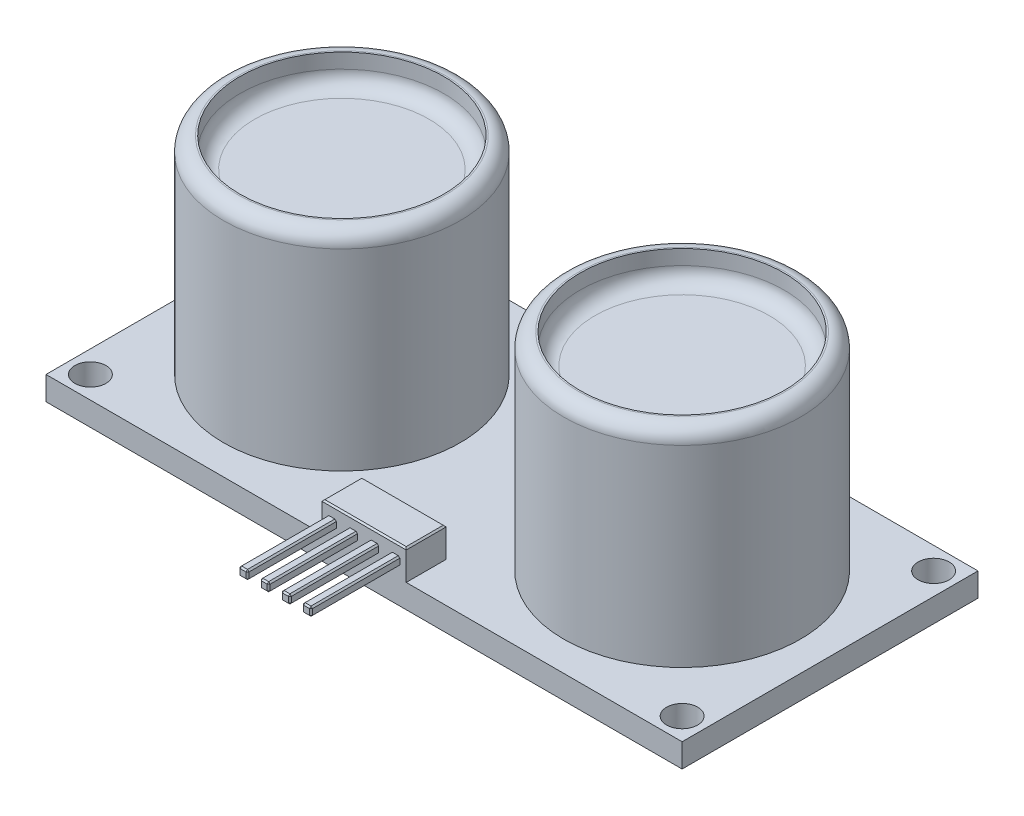
SolidWorks part; units mm, degrees
ref_plane "Front Plane" through (0, 0, 0) normal (0, 0, 1) x (1, 0, 0)
ref_plane "Top Plane" through (0, 0, 0) normal (0, 1, 0) x (1, 0, 0)
ref_plane "Right Plane" through (0, 0, 0) normal (1, 0, 0) x (0, 0, -1)
sketch "Sketch1" plane through (0, 0, 0) normal (0, 1, 0) x (1, 0, 0)
  line L0 (21.5, 20) -> (21.5, 0) construction
  line L1 (0, 0) -> (43, 0)
  line L2 (0, 0) -> (0, 20)
  line L3 (0, 20) -> (43, 20)
  line L4 (43, 0) -> (43, 20)
  dimension "D1" = 20
  dimension "D2" = 43
extrude "Boss-Extrude1" add sketch "Sketch1" along normal blind 1.6
sketch "Sketch2" plane through (0, 1.6, 0) normal (0, 1, 0) x (1, 0, 0)
  line L0 (0, 10) -> (43, 10) construction
  line L1 (0, 20) -> (0, 0) construction
  line L2 (43, 0) -> (43, 20) construction
  circle A0 centre (10, 10) radius 8
  dimension "D1" = 16
  dimension "D2" = 10
extrude "Boss-Extrude2" add sketch "Sketch2" along normal blind 14
sketch "Sketch3" plane through (0, 15.6, 0) normal (0, 1, 0) x (1, 0, 0)
  circle A0 centre (10, 10) radius 6.894
extrude "Cut-Extrude1" cut sketch "Sketch3" against normal blind 2
fillet "Fillet1" radius 1 1 edges at (10, 15.6, -2)
fillet "Fillet2" radius 1 1 edges at (10, 13.6, -3.106)
ref_axis "Axis1" through (21.5, 0, -20) along (0, 0, 1)
ref_plane "Plane1" through (21.5, 0, 0) normal (1, 0, 0) x (0, 0, -1)
mirror "Mirror1" about plane through (21.5, 0, 0) normal (1, 0, 0) of "Fillet2", "Fillet1", "Cut-Extrude1", "Boss-Extrude2"
sketch "Sketch4" plane through (0, 1.6, 0) normal (0, 1, 0) x (1, 0, 0)
  line L0 (21.5, 0) -> (18.65, 0)
  line L1 (0, 0) -> (43, 0) construction
  line L2 (21.5, 0) -> (24.35, 0)
  line L3 (18.65, 0) -> (18.65, 2.7)
  line L4 (18.65, 2.7) -> (24.35, 2.7)
  line L5 (24.35, 2.7) -> (24.35, 0)
  dimension "D1" = 2.85
  dimension "D2" = 2.85
  dimension "D3" = 2.7
extrude "Boss-Extrude3" add sketch "Sketch4" along normal blind 2
sketch "Sketch5" plane through (0, 0, 0) normal (0, 0, 1) x (1, 0, 0)
  line L0 (18.65, 2.6) -> (24.35, 2.6) construction
  line L1 (18.65, 3.6) -> (18.65, 1.6) construction
  line L2 (24.35, 3.6) -> (24.35, 1.6) construction
  line L3 (20.4525, 2.3) -> (21.0525, 2.9) construction
  line L4 (19.0225, 2.3) -> (19.6225, 2.3)
  line L5 (19.0225, 2.3) -> (19.0225, 2.9)
  line L6 (19.0225, 2.9) -> (19.6225, 2.9)
  line L7 (19.6225, 2.3) -> (19.6225, 2.9)
  line L8 (19.0225, 2.3) -> (19.6225, 2.9) construction
  line L9 (19.0225, 2.9) -> (19.6225, 2.3) construction
  line L10 (20.4525, 2.9) -> (21.0525, 2.3) construction
  line L11 (20.4525, 2.3) -> (20.4525, 2.9)
  line L12 (20.4525, 2.3) -> (21.0525, 2.3)
  line L13 (21.0525, 2.3) -> (21.0525, 2.9)
  line L14 (20.4525, 2.9) -> (21.0525, 2.9)
  line L15 (21.8825, 2.3) -> (22.4825, 2.9) construction
  line L16 (21.8825, 2.9) -> (22.4825, 2.3) construction
  line L17 (21.8825, 2.3) -> (21.8825, 2.9)
  line L18 (21.8825, 2.3) -> (22.4825, 2.3)
  line L19 (22.4825, 2.3) -> (22.4825, 2.9)
  line L20 (21.8825, 2.9) -> (22.4825, 2.9)
  line L21 (23.3125, 2.3) -> (23.9125, 2.9) construction
  line L22 (23.3125, 2.9) -> (23.9125, 2.3) construction
  line L23 (23.3125, 2.3) -> (23.3125, 2.9)
  line L24 (23.3125, 2.3) -> (23.9125, 2.3)
  line L25 (23.9125, 2.3) -> (23.9125, 2.9)
  line L26 (23.3125, 2.9) -> (23.9125, 2.9)
  point P6 (19.3225, 2.6)
  point P12 (20.7525, 2.6)
  point P17 (22.1825, 2.6)
  point P22 (23.6125, 2.6)
  dimension "D1" = 0.6
  dimension "D2" = 4
extrude "Boss-Extrude4" add sketch "Sketch5" along normal blind 6
chamfer "Chamfer1" distance 0.1 angle 45 32 edges at (23.9125, 2.6, 6) (23.9125, 2.3, 3) (23.6125, 2.3, 6) (23.3125, 2.3, 3) (23.3125, 2.6, 6) (23.9125, 2.9, 3) (23.6125, 2.9, 6) (23.3125, 2.9, 3) (22.4825, 2.6, 6) (22.4825, 2.3, 3) (22.1825, 2.3, 6) (21.8825, 2.3, 3) (21.8825, 2.6, 6) (21.8825, 2.9, 3) (22.1825, 2.9, 6) (22.4825, 2.9, 3) (21.0525, 2.6, 6) (21.0525, 2.3, 3) (20.7525, 2.3, 6) (20.4525, 2.3, 3) (20.4525, 2.6, 6) (21.0525, 2.9, 3) (20.7525, 2.9, 6) (20.4525, 2.9, 3) (19.3225, 2.3, 6) (19.0225, 2.3, 3) (19.0225, 2.6, 6) (19.0225, 2.9, 3) (19.3225, 2.9, 6) (19.6225, 2.3, 3) (19.6225, 2.6, 6) (19.6225, 2.9, 3)
chamfer "Chamfer2" distance 0.1 angle 45 4 edges at (18.65, 3.6, -1.35) (21.5, 3.6, -2.7) (24.35, 3.6, -1.35) (21.5, 3.6, 0)
sketch "Sketch6" plane through (0, 1.6, 0) normal (0, 1, 0) x (1, 0, 0)
  line L0 (21.5, 20) -> (1.5, 20) construction
  line L1 (43, 20) -> (0, 20) construction
  line L2 (21.5, 20) -> (41.5, 20) construction
  line L3 (1.5, 20) -> (1.5, 18.5) construction
  line L4 (1.5, 0) -> (1.5, 1.5) construction
  line L5 (0, 0) -> (18.65, 0) construction
  circle A0 centre (1.5, 18.5) radius 1.05
  circle A1 centre (1.5, 1.5) radius 1.05
  circle A2 centre (41.5, 1.5) radius 1.05
  circle A3 centre (41.5, 18.5) radius 1.05
  dimension "D5" = 2.1
  dimension "D6" = 2.1
  dimension "D7" = 2.1
  dimension "D8" = 2.1
  dimension "D1" = 20
  dimension "D2" = 20
  dimension "D3" = 1.5
  dimension "D4" = 1.5
extrude "Cut-Extrude2" cut sketch "Sketch6" against normal up to next
sketch "Sketch7" plane through (0, 1.6, 0) normal (0, 1, 0) x (1, 0, 0)
  line L0 (1.5, 18.5) -> (41.5, 18.5) construction
  line L1 (21.5, 18.5) -> (21.5, 7.4192) construction
ref_axis "Axis2" through (21.5, 1.6, -18.5) along (0, 0, 1)
